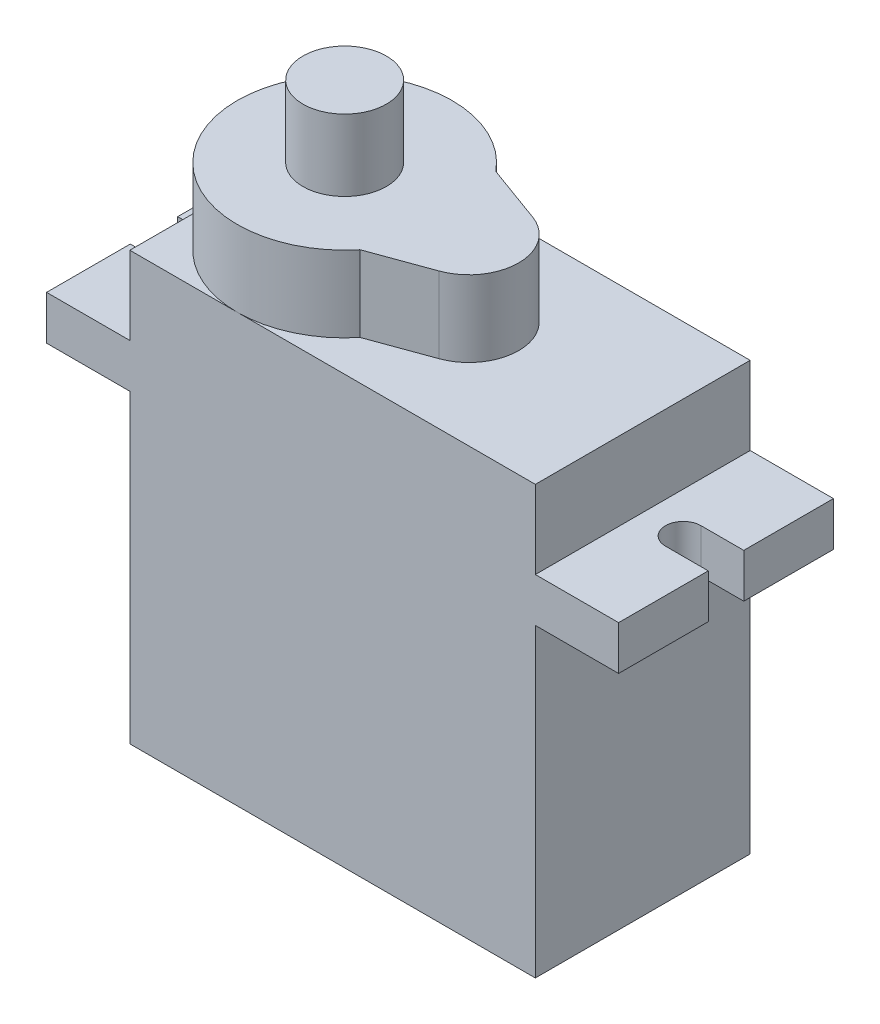
SolidWorks part; units mm, degrees
ref_plane "Front Plane" through (0, 0, 0) normal (0, 0, 1) x (1, 0, 0)
ref_plane "Top Plane" through (0, 0, 0) normal (0, 1, 0) x (1, 0, 0)
ref_plane "Right Plane" through (0, 0, 0) normal (1, 0, 0) x (0, 0, -1)
sketch "Sketch1" plane through (0, 0, 0) normal (0, 1, 0) x (1, 0, 0)
  line L0 (7.9577, 2.6311) -> (4.6916, 3.8199)
  line L1 (-6.05, 6.05) -> (16.79, 6.05)
  line L2 (-6.05, 6.05) -> (-6.05, -6.05)
  line L3 (-6.05, -6.05) -> (16.79, -6.05)
  line L4 (16.79, 6.05) -> (16.79, -6.05)
  line L5 (-6.05, 6.05) -> (16.79, -6.05) construction
  line L6 (-6.05, -6.05) -> (16.79, 6.05) construction
  line L7 (-10.74, 6.05) -> (21.48, 6.05)
  line L8 (-10.74, 6.05) -> (-10.74, -6.05)
  line L9 (-10.74, -6.05) -> (21.48, -6.05)
  line L10 (21.48, 6.05) -> (21.48, -6.05)
  line L11 (-10.74, 6.05) -> (21.48, -6.05) construction
  line L12 (-10.74, -6.05) -> (21.48, 6.05) construction
  line L13 (7, 0) -> (0, 0) construction
  line L14 (7.9577, -2.6311) -> (4.6916, -3.8199)
  line L15 (-8.33, 0) -> (19.07, 0) construction
  line L16 (-8.33, 1.3333) -> (-10.74, 1.3333)
  line L17 (-8.33, -1.3333) -> (-10.74, -1.3333)
  line L18 (19.07, 1) -> (21.48, 1)
  line L19 (19.07, -1) -> (21.48, -1)
  circle A0 centre (0, 0) radius 6.05
  circle A1 centre (0, 0) radius 2.35
  circle A2 centre (7, 0) radius 2.8
  circle A3 centre (-8.33, 0) radius 1.3333
  circle A4 centre (19.07, 0) radius 1
  point P3 (5.37, 0)
  point P10 (5.37, 0)
  point P25 (5.37, 0)
  dimension "D4" = 4.7
  dimension "D5" = 5.6
  dimension "D9" = 2
  dimension "D10" = 2.6667
  dimension "D1" = 12.1
  dimension "D2" = 22.84
  dimension "D3" = 32.22
  dimension "D6" = 7
  dimension "D7" = 20
  dimension "D8" = 27.4
extrude "Boss-Extrude1" add sketch "Sketch1" against normal blind 17.2 contours L2 L3 L4 L1
extrude "Boss-Extrude2" add sketch "Sketch1<3>" along normal blind 2.48 contours A3 L17 L8 L9 L2 L7 L16 | A4 L18 L10 L7 L4 L9 L19 | L1 L4 L3 L2 region at (-6.1798, 0, -3.025) region at (19.135, 0, -5.9202)
sketch "Sketch1<3>" plane through (0, 0, 0) normal (0, 1, 0) x (1, 0, 0) same geometry as "Sketch1"
extrude "Boss-Extrude3" add sketch "Sketch1<4>" along normal blind 4.4 from surface contours L4 L3 L2 L1 starting at face at (5.3978, 2.48, 0)
sketch "Sketch1<4>" plane through (0, 0, 0) normal (0, 1, 0) x (1, 0, 0) same geometry as "Sketch1"
extrude "Boss-Extrude4" add sketch "Sketch1<5>" along normal blind 4.28 from surface contours A2 A0 A1 | A2 A0 L14 | A2 L0 A0 | A0 A2 | A2 A0 | A1 region at (5.8814, 0, -3.0527) region at (7.6067, 0, 0) region at (5.0288, 0, -3.0518) region at (5.1941, 0, 0) region at (5.8814, 0, 3.0527) region at (0, 0, 0) starting at face at (5.37, 6.88, 0)
sketch "Sketch1<5>" plane through (0, 0, 0) normal (0, 1, 0) x (1, 0, 0) same geometry as "Sketch1"
extrude "Boss-Extrude5" add sketch "Sketch1<6>" along normal blind 4.02 from surface contours A1 starting at face at (4.0998, 11.16, 0)
sketch "Sketch1<6>" plane through (0, 0, 0) normal (0, 1, 0) x (1, 0, 0) same geometry as "Sketch1"
